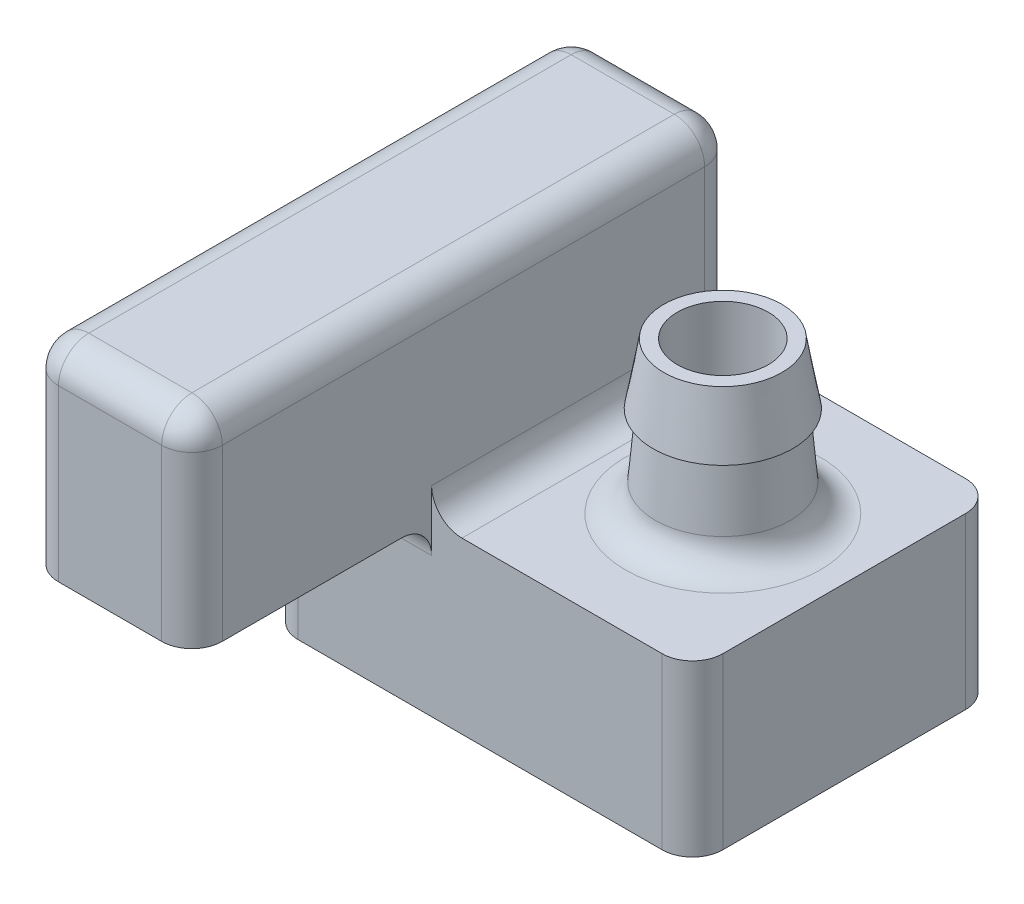
SolidWorks part; units mm, degrees
ref_plane "Front Plane" through (0, 0, 0) normal (0, 0, 1) x (1, 0, 0)
ref_plane "Top Plane" through (0, 0, 0) normal (0, 1, 0) x (1, 0, 0)
ref_plane "Right Plane" through (0, 0, 0) normal (1, 0, 0) x (0, 0, -1)
sketch "Sketch1" plane through (0, 0, 0) normal (0, 1, 0) x (1, 0, 0)
  line L0 (0, -1.9) -> (0, 1.9) construction
  line L1 (-2.9, 1.9) -> (2.9, 1.9)
  line L2 (-2.9, 1.9) -> (-2.9, -1.9)
  line L3 (-2.9, -1.9) -> (2.9, -1.9)
  line L4 (2.9, 1.9) -> (2.9, -1.9)
  line L5 (-3.5, 2.5) -> (3.5, 2.5)
  line L6 (-3.5, 2.5) -> (-3.5, -2.5)
  line L7 (-3.5, -2.5) -> (3.5, -2.5)
  line L8 (3.5, 2.5) -> (3.5, -2.5)
  line L9 (-3.5, 0) -> (3.5, 0) construction
  point P10 (0, 0)
  point P14 (0, 0)
  dimension "D1" = 7
  dimension "D2" = 5
  dimension "D3" = 0.6
  dimension "D4" = 0.6
extrude "Boss-Extrude1" add sketch "Sketch1" along normal blind 2.8
sketch "Sketch2" plane through (0, 2.8, 0) normal (0, 1, 0) x (1, 0, 0)
  line L0 (0, 0) -> (0, -5.5) construction
  line L1 (0, -5.5) -> (0, -8.25) construction
  line L2 (0, -8.25) -> (-2.15, -8.25) construction
  line L3 (-2.15, -8.25) -> (-2.15, -4.85) construction
  point P8 (0, -5.5)
  dimension "D1" = 2.75
  dimension "D2" = 5.5
  dimension "D3" = 2.15
  dimension "D4" = 3.4
ref_point "SDP3X center"
ref_point "SDP3X neg press port"
sketch "Sketch3" plane through (0, 2.8, 0) normal (0, 1, 0) x (1, 0, 0)
  line L0 (-2.15, 0.0001) -> (-2.15, -4.85) construction
  line L1 (-3.5, 2.5) -> (-0.8, 2.5)
  line L2 (-3.5, 2.5) -> (-3.5, -6.45)
  line L3 (-3.5, -6.45) -> (-0.8, -6.45)
  line L4 (-0.8, 2.5) -> (-0.8, -6.45)
  line L5 (-2.9, 1.9) -> (-1.4, 1.9)
  line L6 (-2.9, 1.9) -> (-2.9, -5.85)
  line L7 (-2.9, -5.85) -> (-1.4, -5.85)
  line L8 (-1.4, 1.9) -> (-1.4, -5.85)
  line L9 (-1.4, -5.85) -> (-0.8, -5.85) construction
  line L10 (-1.4, -5.85) -> (-1.4, -6.45) construction
  point P13 (0, 0)
  dimension "D1" = 1
extrude "Boss-Extrude2" add sketch "Sketch3" along normal offset from surface (2.7 mm away) 5.5 up to face at (0, 0, 0)
sketch "Sketch4" plane through (0, 2.8, 0) normal (0, -1, 0) x (1, 0, 0)
  line L0 (-0.8, 1.9) -> (-0.8, -1.9) construction
  line L1 (-3.5, 6.45) -> (-0.8, 6.45)
  line L2 (-3.5, 6.45) -> (-3.5, 1.9)
  line L3 (-3.5, 1.9) -> (-0.8, 1.9)
  line L4 (-0.8, 6.45) -> (-0.8, 1.9)
  point P7 (-0.8, 1.9)
  point P8 (-0.8, 1.9)
extrude "Boss-Extrude3" add sketch "Sketch4" against normal blind 0.6
sketch "Sketch5" plane through (0, 5.5, 0) normal (0, 1, 0) x (1, 0, 0)
  line L1 (-3.5, 2.5) -> (-0.8, 2.5)
  line L2 (-3.5, 2.5) -> (-3.5, -6.45)
  line L3 (-3.5, -6.45) -> (-0.8, -6.45)
  line L4 (-0.8, 2.5) -> (-0.8, -6.45)
extrude "Boss-Extrude4" add sketch "Sketch5" along normal blind 0.6
sketch "Sketch6" plane through (0, 2.8, 0) normal (0, 1, 0) x (1, 0, 0)
  line L0 (-1.4, -1.9) -> (-1.4, 1.9) construction
  line L1 (-1.4, -2.5) -> (3.5, -2.5)
  line L2 (-1.4, -2.5) -> (-1.4, 2.5)
  line L3 (-1.4, 2.5) -> (3.5, 2.5)
  line L4 (3.5, -2.5) -> (3.5, 2.5)
  point P4 (-0.8, -2.5)
  point P5 (3.5, -2.5)
extrude "Boss-Extrude5" add sketch "Sketch6" against normal blind 0.6
fillet "Fillet2" radius 0.7 4 edges at (-2.15, 5.5, -1.9) (-2.15, 5.5, 5.85) (-1.4, 5.5, 1.975) (-2.9, 5.5, 1.975)
sketch "Sketch7" plane through (0, 2.8, 0) normal (0, -1, 0) x (1, 0, 0)
  circle A0 centre (-2.15, 4.85) radius 1
  dimension "D1" = 2
extrude "Cut-Extrude1" cut sketch "Sketch7" against normal offset from surface (1.7 mm away) 4.5 up to face at (0, 0, 0)
sketch "Sketch8" plane through (0, 2.8, 0) normal (0, -1, 0) x (-1, 0, 0)
  line L0 (0, 0) -> (-1.5, 0) construction
  circle A0 centre (-1.5, 0) radius 1.15
  dimension "D1" = 1.5
  dimension "D2" = 2.3
extrude "Boss-Extrude6" add sketch "Sketch8" against normal blind 1.5 draft 5
fillet "Fillet1" radius 0.5 1 edges at (1.5, 2.8, 1.15)
extrude "Boss-Extrude7" add sketch "Sketch8<2>" against normal blind 1 draft 10 from surface starting at face at (1.5, 4.3, -1.0188)
sketch "Sketch8<2>" plane through (0, 2.8, 0) normal (0, -1, 0) x (-1, 0, 0) same geometry as "Sketch8"
sketch "Sketch9" plane through (0, 5.3, 0) normal (0, 1, 0) x (1, 0, 0)
  circle A0 centre (1.5, 0) radius 0.75
  dimension "D1" = 1.5
extrude "Cut-Extrude2" cut sketch "Sketch9" against normal through all both and the other way through all
fillet "Fillet3" radius 0.5 4 edges at (-2.15, 6.1, 6.45) (-2.15, 6.1, -2.5) (-3.5, 6.1, 1.975) (-0.8, 6.1, 1.975)
fillet "Fillet5" radius 0.5 11 edges at (-0.9464, 5.9536, -2.3536) (-3.3536, 5.9536, -2.3536) (3.5, 1.4, 2.5) (3.5, 1.4, -2.5) (-0.8, 4.2, -2.5) (-3.5, 2.8, -2.5) (-3.5, 1.4, 2.5) (-3.3536, 5.9536, 6.3036) (-0.9464, 5.9536, 6.3036) (-3.5, 4.2, 6.45) (-0.8, 4.2, 6.45)
fillet "Fillet6" radius 0.5 2 edges at (-0.9464, 2.8, -2.3536) (-0.8, 2.8, 0.25)
fillet "Fillet7" radius 0.5 2 edges at (-3.3536, 2.8, 2.3536) (-1.9, 2.8, 2.5)
chamfer "Chamfer1" distance 0.5 angle 45 1 edges at (-2.15, 3.4, 1.9)
